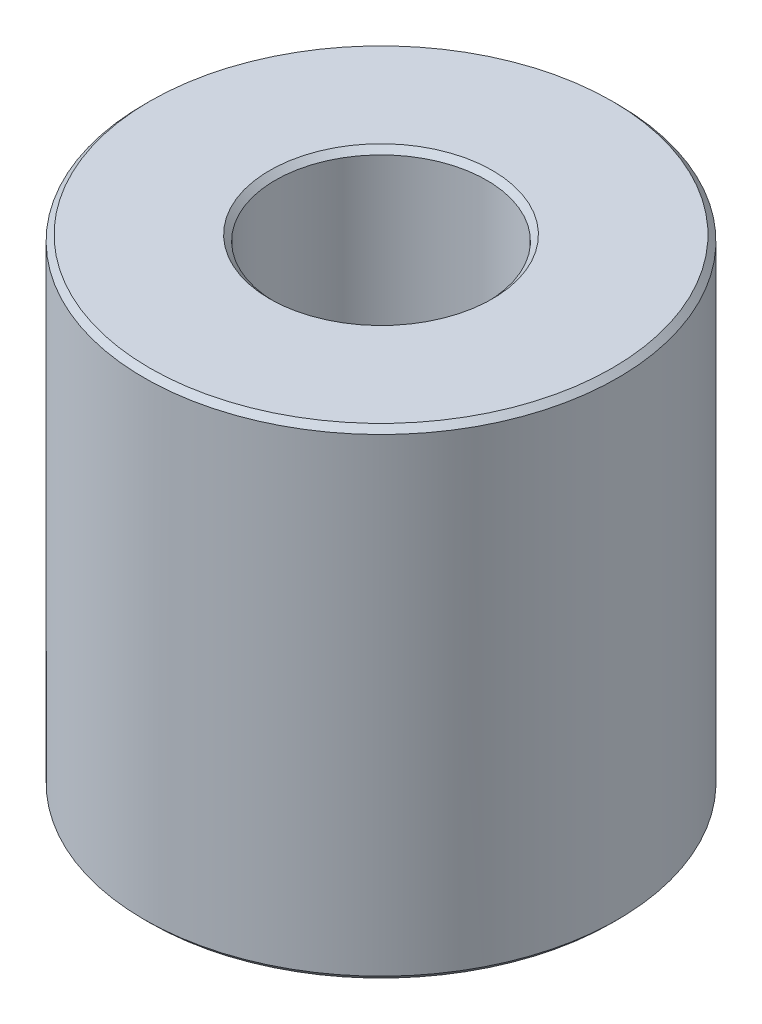
SolidWorks part; units mm, degrees
ref_plane "Front Plane" through (0, 0, 0) normal (0, 0, 1) x (1, 0, 0)
ref_plane "Top Plane" through (0, 0, 0) normal (0, 1, 0) x (1, 0, 0)
ref_plane "Right Plane" through (0, 0, 0) normal (1, 0, 0) x (0, 0, -1)
sketch "Sketch1" plane through (0, 0, 0) normal (0, 1, 0) x (1, 0, 0)
  circle A0 centre (0, 0) radius 35
  dimension "SLEEVE_OD" = 70
extrude "Boss-Extrude1" add sketch "Sketch1" along normal blind 70.9919
sketch "Sketch2" plane through (0, 0, 0) normal (0, 1, 0) x (1, 0, 0)
  circle A0 centre (0, 0) radius 15.6183
  dimension "BORE_D" = 31.2366
extrude "Cut-Extrude1" cut sketch "Sketch2" along normal through all
chamfer "Chamfer1" distance 0.8341 angle 45 4 edges at (0, 70.9919, 15.6183) (0, 0, 15.6183) (0, 0, 35) (0, 70.9919, 35)
